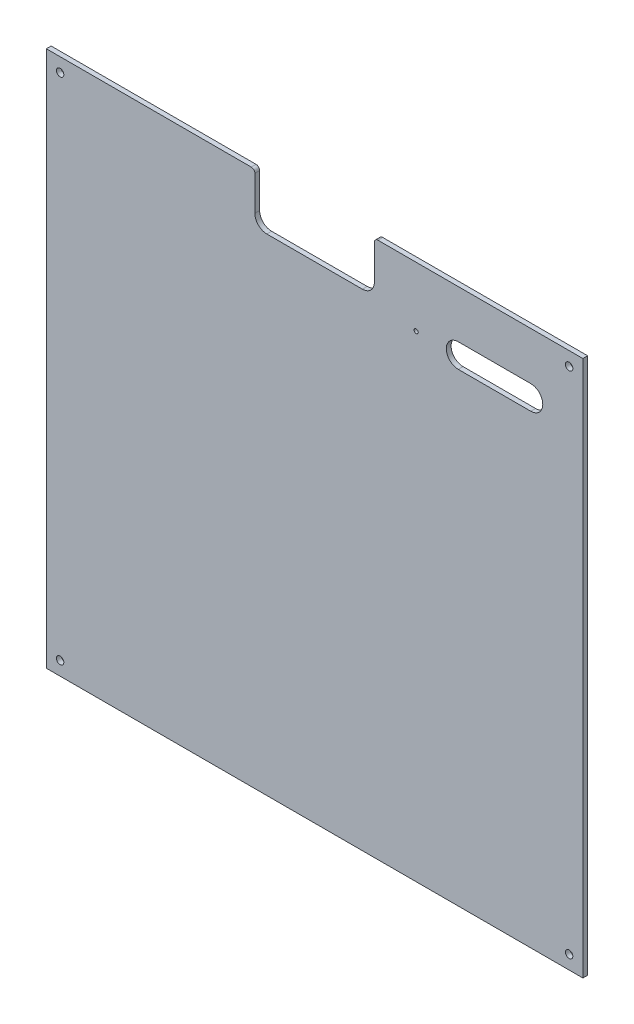
SolidWorks part; units mm, degrees
material "ABS PC"
ref_plane "Piano frontale" through (0, 0, 0) normal (0, 0, 1) x (1, 0, 0)
ref_plane "Piano superiore" through (0, 0, 0) normal (0, 1, 0) x (1, 0, 0)
ref_plane "Piano destro" through (0, 0, 0) normal (1, 0, 0) x (0, 0, -1)
sketch "Schizzo1" plane through (0, 0, 0) normal (0, 0, 1) x (1, 0, 0)
  line L0 (0, 0) -> (0, 449)
  line L1 (0, 449) -> (171.5, 449)
  line L2 (449, 449) -> (449, 0)
  line L3 (449, 0) -> (0, 0)
  line L4 (174.5, 446) -> (174.5, 417)
  line L5 (184.5, 407) -> (264.5, 407)
  line L6 (274.5, 417) -> (274.5, 446)
  line L7 (277.5, 449) -> (449, 449)
  line L8 (154.5, 399) -> (294.5, 399) construction
  line L9 (224.5, 379) -> (224.5, 419) construction
  line L10 (344.7159, 399) -> (405.4404, 399) construction
  line L11 (344.7159, 409) -> (405.4404, 409)
  line L12 (344.7159, 389) -> (405.4404, 389)
  line L13 (0, 224.5) -> (449, 224.5) construction
  line L23 (73.9219, 399) -> (73.9219, 449) construction
  line L24 (174.5, 431.5) -> (314.5, 431.5) construction
  arc A0 (174.5, 417) -> (184.5, 407) centre (184.5, 417) ccw
  arc A1 (274.5, 417) -> (264.5, 407) centre (264.5, 417) cw
  circle A2 centre (11.5, 11.5) radius 3.1
  circle A3 centre (437.5, 11.5) radius 3.1
  circle A4 centre (437.5, 437.5) radius 3.1
  circle A5 centre (11.5, 437.5) radius 3.1
  circle A6 centre (309.5, 399) radius 1.75
  arc A7 (277.5, 449) -> (274.5, 446) centre (277.5, 446) ccw
  arc A8 (344.7159, 409) -> (344.7159, 389) centre (344.7159, 399) ccw
  arc A9 (405.4404, 389) -> (405.4404, 409) centre (405.4404, 399) ccw
  arc A10 (174.5, 446) -> (171.5, 449) centre (171.5, 446) ccw
  point P11 (174.5, 407)
  point P14 (274.5, 407)
  point P33 (375.0781, 399)
  point P44 (174.5, 449)
  dimension "D5" = 10
  dimension "D6" = 11.5
  dimension "D7" = 11.5
  dimension "D8" = 6.2
  dimension "D9" = 3.5
  dimension "D10" = 35
  dimension "D12" = 3
  dimension "D1" = 449
  dimension "D2" = 449
  dimension "D3" = 100
  dimension "D4" = 42
  dimension "D11" = 20
  dimension "D21" = 50
extrude "Estrusione-Estrusione1" add sketch "Schizzo1" along normal blind 4
